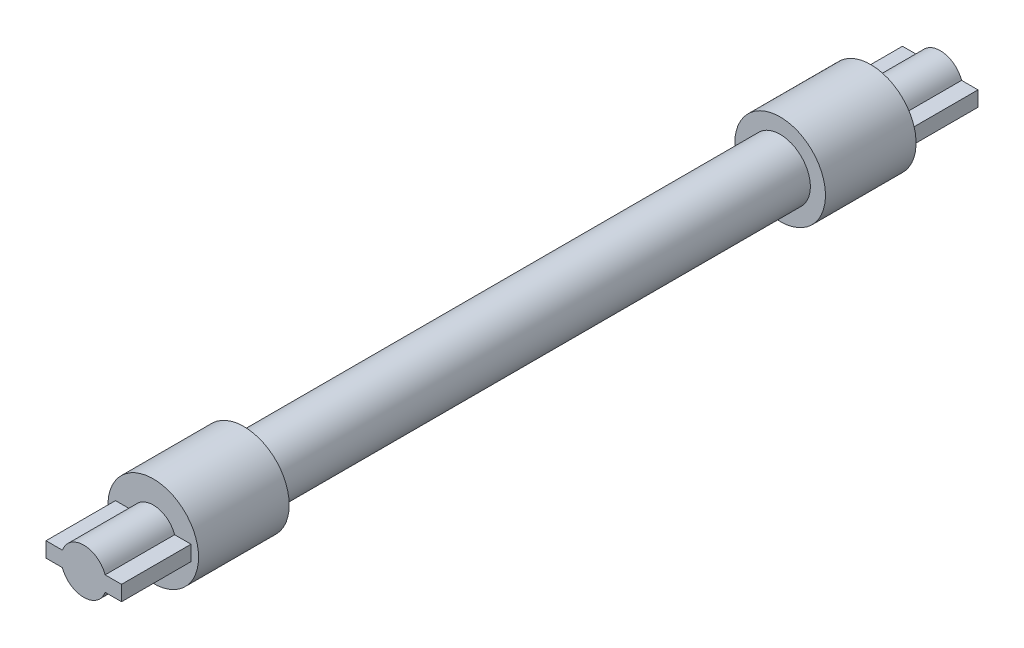
SolidWorks part; units mm, degrees
ref_plane "Front" through (0, 0, 0) normal (0, 0, 1) x (1, 0, 0)
ref_plane "Top" through (0, 0, 0) normal (0, 1, 0) x (1, 0, 0)
ref_plane "Right" through (0, 0, 0) normal (1, 0, 0) x (0, 0, -1)
sketch "Sketch1" plane through (0, 0, 0) normal (0, 0, 1) x (1, 0, 0)
  circle A0 centre (0, 0) radius 40
extrude "Boss-Extrude1" add sketch "Sketch1" along normal blind 710
sketch "Sketch2" plane through (0, 0, 710) normal (0, 0, 1) x (1, 0, 0)
  circle A0 centre (0, 0) radius 60
  dimension "D1" = 120
extrude "Boss-Extrude2" add sketch "Sketch2" along normal blind 120
sketch "Sketch3" plane through (0, 0, 0) normal (0, 0, -1) x (-1, 0, 0)
  circle A0 centre (0, 0) radius 60
  dimension "D1" = 120
extrude "Boss-Extrude3" add sketch "Sketch3" along normal blind 120
sketch "Sketch4" plane through (0, 0, 830) normal (0, 0, 1) x (1, 0, 0)
  line L0 (-50, 10) -> (50, 10)
  line L1 (-50, 10) -> (-50, -10)
  line L2 (-50, -10) -> (50, -10)
  line L3 (50, 10) -> (50, -10)
  circle A0 centre (0, 0) radius 30
  dimension "D5" = 60
  dimension "D1" = 50
  dimension "D2" = 100
  dimension "D3" = 10
  dimension "D4" = 20
extrude "Boss-Extrude4" add sketch "Sketch4" along normal blind 92 contours A0 L0 L1 L2 | L0 A0 | L0 A0 L2 | L2 A0 | A0 L2 L3 L0 region at (-39.7111, 0, 830) region at (0, 18.2843, 830) region at (0, 0, 830) region at (39.7111, 0, 830) region at (0, -18.2843, 830)
sketch "Sketch5" plane through (0, 0, -120) normal (0, 0, -1) x (-1, 0, 0)
  line L0 (50, -10) -> (-50, -10)
  line L1 (50, -10) -> (50, 10)
  line L2 (50, 10) -> (-50, 10)
  line L3 (-50, -10) -> (-50, 10)
  circle A0 centre (0, 0) radius 30
  dimension "D3" = 60
  dimension "D1" = 50
  dimension "D2" = 100
  dimension "D4" = 10
  dimension "D5" = 20
extrude "Boss-Extrude5" add sketch "Sketch5" along normal blind 92 contours L2 A0 | A0 L2 L3 L0 | L2 A0 L0 | L0 A0 | A0 L0 L1 L2 region at (-39.7111, 0, -120) region at (0, -18.2843, -120) region at (0, 0, -120) region at (39.7111, 0, -120) region at (0, 18.2843, -120)
